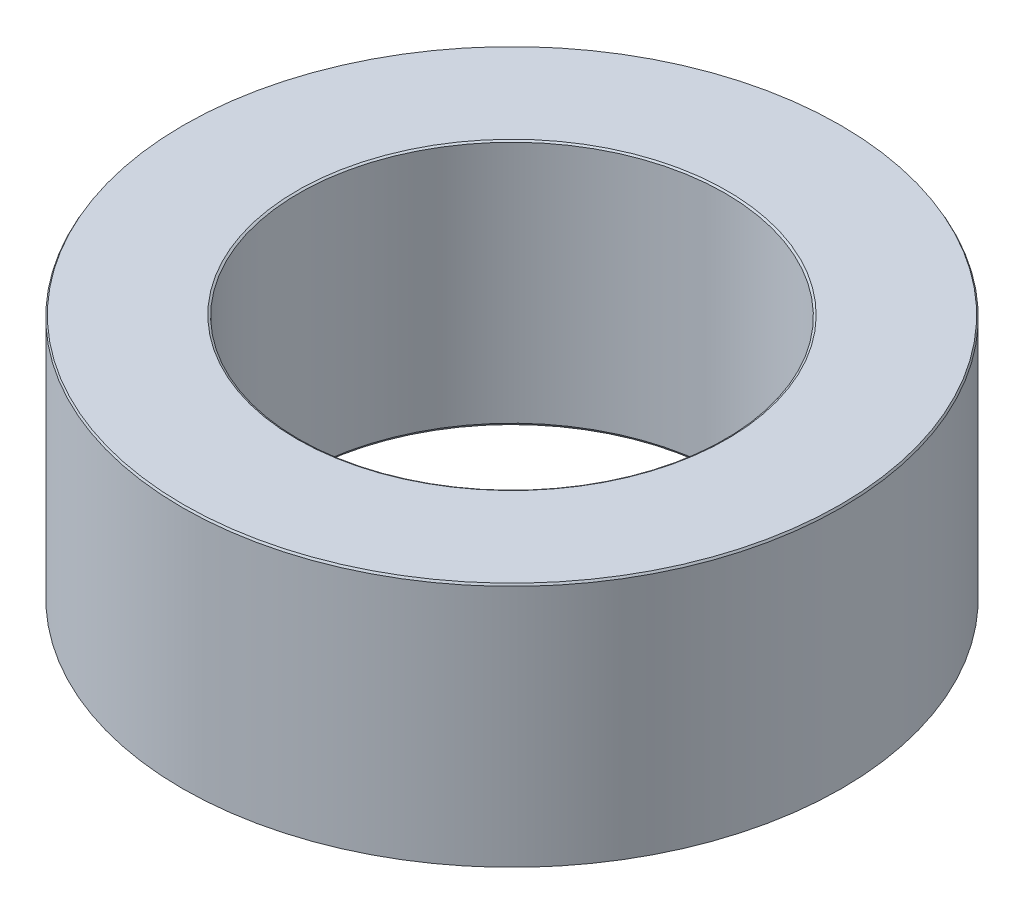
SolidWorks part; units mm, degrees
ref_plane "Front Plane" through (0, 0, 0) normal (0, 0, 1) x (1, 0, 0)
ref_plane "Top Plane" through (0, 0, 0) normal (0, 1, 0) x (1, 0, 0)
ref_plane "Right Plane" through (0, 0, 0) normal (1, 0, 0) x (0, 0, -1)
sketch "Sketch1" plane through (0, 0, 0) normal (0, 1, 0) x (1, 0, 0)
  circle A0 centre (0, 0) radius 57.5
  dimension "SLEEVE_OD" = 115
extrude "Boss-Extrude1" add sketch "Sketch1" along normal blind 42.9854
sketch "Sketch2" plane through (0, 0, 0) normal (0, 1, 0) x (1, 0, 0)
  circle A0 centre (0, 0) radius 37.1667
  dimension "BORE_D" = 74.3333
extrude "Cut-Extrude1" cut sketch "Sketch2" along normal through all
chamfer "Chamfer1" distance 0.347 angle 30 4 edges at (0, 42.9854, 37.1667) (0, 0, 37.1667) (0, 0, 57.5) (0, 42.9854, 57.5) first distance on face at (0, 42.9854, 37.1667) first distance on face at (0, 0, 37.1667) first distance on face at (0, 42.9854, 57.5)
